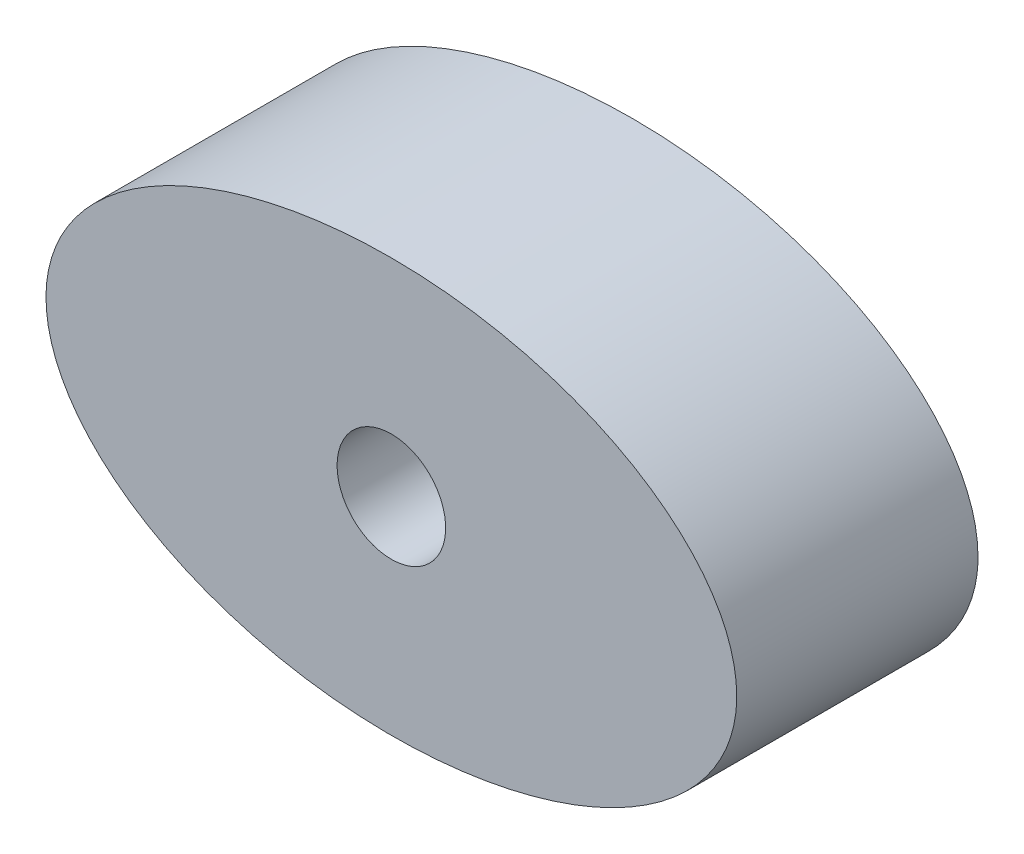
SolidWorks part; units mm, degrees
ref_plane "Plan de face" through (0, 0, 0) normal (0, 0, 1) x (1, 0, 0)
ref_plane "Plan de dessus" through (0, 0, 0) normal (0, 1, 0) x (1, 0, 0)
ref_plane "Plan de droite" through (0, 0, 0) normal (1, 0, 0) x (0, 0, -1)
sketch "Esquisse1" plane through (0, 0, 0) normal (0, 0, 1) x (1, 0, 0)
  ellipse E0 centre (0, 0) end of major axis (21.209, 0) minor radius 12.7
extrude "Boss.-Extru.1" add sketch "Esquisse1" along normal blind 14.8158
sketch "Esquisse2" plane through (0, 0, 0) normal (0, 0, -1) x (-1, 0, 0)
  circle A0 centre (0, 0) radius 3.3337
extrude "Enlèv. mat.-Extru.1" cut sketch "Esquisse2" against normal through all
